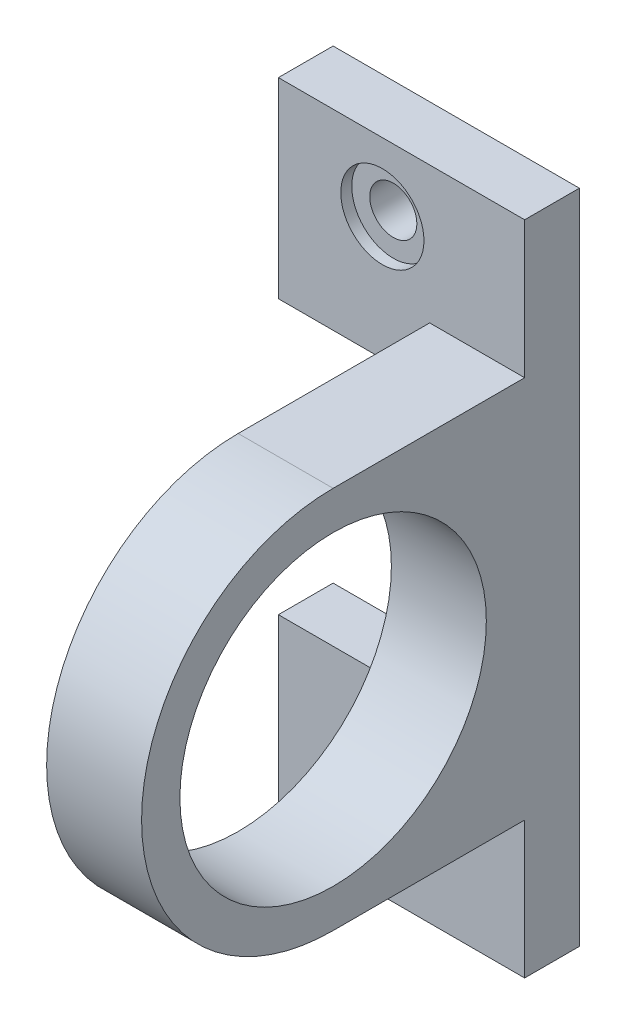
SolidWorks part; units mm, degrees
ref_plane "前视基准面" through (0, 0, 0) normal (0, 0, 1) x (1, 0, 0)
ref_plane "上视基准面" through (0, 0, 0) normal (0, 1, 0) x (1, 0, 0)
ref_plane "右视基准面" through (0, 0, 0) normal (1, 0, 0) x (0, 0, -1)
sketch "草图2" plane through (0, 0, 0) normal (0, 0, 1) x (1, 0, 0)
  line L0 (-14.7736, 24.3382) -> (-14.7736, -35.6618)
  line L1 (-14.7736, -35.6618) -> (30.2264, -35.6618)
  line L2 (7.7264, -35.6618) -> (7.7264, -18.1618)
  line L3 (21.55, -18.1618) -> (-6.0971, -18.1618)
  line L4 (-6.0971, -18.1618) -> (-6.0971, 6.8382)
  line L5 (-6.0971, 6.8382) -> (21.55, 6.8382)
  line L6 (7.7264, 6.8382) -> (7.7264, 24.3382)
  line L7 (30.2264, 24.3382) -> (-14.7736, 24.3382)
  line L8 (7.7264, 28.8603) -> (7.7264, -39.8897) construction
  line L9 (21.55, -18.1618) -> (21.55, 6.8382)
  line L10 (30.2264, 24.3382) -> (30.2264, -35.6618)
  line L11 (-18.1559, -5.6618) -> (33.2411, -5.6618) construction
  line L12 (44.0218, -5.6618) -> (44.0218, 26.2521) construction
  point P16 (-6.0971, -5.6618)
  point P17 (-14.7736, -5.6618)
  dimension "D1" = 45
  dimension "D2" = 25
  dimension "D3" = 60
extrude "凸台-拉伸2" add sketch "草图2" along normal blind 5 contours L6 L7 L0 L1 L2 L3 L4 L5 | L10 L7 L6 L5 L9 L3 L2 L1 region at (-3.5236, 23.6974, 0) region at (18.9764, 23.6974, 0)
sketch "草图4" plane through (0, 0, 5) normal (0, 0, 1) x (1, 0, 0)
  line L0 (-18.165, -5.6618) -> (33.9165, -5.6618) construction
  line L1 (-14.7736, 24.3382) -> (-14.7736, -35.6618) construction
  line L2 (-14.7736, -23.1618) -> (-6.0971, -23.1618)
  line L3 (-14.7736, -23.1618) -> (-14.7736, 11.8382)
  line L4 (-14.7736, 11.8382) -> (-6.0971, 11.8382)
  line L5 (-6.0971, -23.1618) -> (-6.0971, 11.8382)
  line L6 (-6.0971, -18.1618) -> (-6.0971, 6.8382) construction
  line L7 (7.7264, -39.813) -> (7.7264, 28.1228) construction
  line L8 (30.2264, 11.8382) -> (21.55, 11.8382)
  line L9 (21.55, -23.1618) -> (21.55, 11.8382)
  line L10 (30.2264, -23.1618) -> (21.55, -23.1618)
  line L11 (30.2264, -23.1618) -> (30.2264, 11.8382)
  point P17 (-14.7736, -5.6618)
  dimension "D1" = 35
extrude "凸台-拉伸15" add sketch "草图4" along normal blind 35
sketch "草图5" plane through (-14.7736, 0, 0) normal (-1, 0, 0) x (0, 0, 1)
  line L0 (0, -5.6618) -> (40, -5.6618)
  line L1 (0, 24.3382) -> (0, -35.6618) construction
  line L2 (40, 11.8382) -> (40, -23.1618) construction
  line L3 (22.5, 11.8382) -> (40, 11.8382)
  line L4 (40, 11.8382) -> (40, -23.1618)
  line L5 (40, -23.1618) -> (22.5, -23.1618)
  circle A0 centre (22.5, -5.6618) radius 17.5
  line M5 (5, -23.1618) -> (40, -23.1618)
  line M6 (40, -23.1618) -> (40, 11.8382)
  line M7 (40, 11.8382) -> (5, 11.8382)
  dimension "D1" = 35
extrude "切除-拉伸1" cut sketch "草图5" against normal blind 45 contours A0 M5 M6 | A0 M6 M7 region at (-14.7736, 7.9293, 36.0911) region at (-14.7736, -19.2528, 36.0911)
sketch "草图6" plane through (-14.7736, 0, 0) normal (-1, 0, 0) x (0, 0, 1)
  circle A0 centre (22.5, -5.6618) radius 14
  dimension "D1" = 28
extrude "切除-拉伸2" cut sketch "草图6" against normal blind 45
fillet "圆角1" radius 5 4 edges at (-6.0971, 6.8382, 2.5) (21.55, 6.8382, 2.5) (-6.0971, -18.1618, 2.5) (21.55, -18.1618, 2.5)
sketch "草图7" plane through (-6.0971, 0, 0) normal (1, 0, 0) x (0, 0, -1)
  circle A0 centre (-22.5, -5.6618) radius 15
  circle A1 centre (-22.5, -5.6618) radius 13
extrude "凸台-拉伸16" add sketch "草图7" against normal blind 1
sketch "草图8" plane through (21.55, 0, 0) normal (-1, 0, 0) x (0, 0, 1)
  circle A0 centre (22.5, -5.6618) radius 15
  circle A1 centre (22.5, -5.6618) radius 10
sketch "草图9" plane through (0, 0, 5) normal (0, 0, 1) x (1, 0, 0)
  line L0 (7.7264, 24.3382) -> (7.7264, -35.6618)
  line L13 (30.2264, 24.3382) -> (-14.7736, 24.3382) construction
  line L14 (-14.7736, -35.6618) -> (30.2264, -35.6618) construction
sketch "草图11" plane through (0, 0, 5) normal (0, 0, 1) x (1, 0, 0)
  line L0 (-14.7736, 18.0882) -> (30.2264, 18.0882)
  line L1 (-14.7736, 24.3382) -> (-14.7736, 11.8382) construction
  line L2 (30.2264, 24.3382) -> (30.2264, 11.8382) construction
  line L3 (7.7264, 24.3382) -> (7.7264, -35.6618) construction
  line L4 (30.2264, 24.3382) -> (-14.7736, 24.3382) construction
  line L5 (-14.7736, -35.6618) -> (30.2264, -35.6618) construction
  line L6 (7.7264, -5.6618) -> (45.6912, -5.6618) construction
  line L10 (-14.7736, -29.4118) -> (30.2264, -29.4118)
  line L11 (-14.7736, -23.1618) -> (-14.7736, -35.6618) construction
  point P4 (-1.7736, 18.0882)
  point P16 (-1.7736, -29.4118)
  point P18 (17.2264, -29.4118)
  point P25 (17.2264, 18.0882)
  dimension "D1" = 13
split "分割1" trim tools "草图9" bodies to split 111 resulting bodies 117 118
delete or keep bodies "实体-删除/保留 2" type delete bodies bodies 117
hole_wizard "打孔尺寸(%根据六角头螺)栓 全螺纹的类型1" positions "3D草图2" profile "草图13" counterbore size "M4" standard "GB"
sketch3d "3D草图2"
  point P0 (17.2264, 18.0882, 5)
  point P3 (17.2264, -29.4118, 5)
sketch "草图13" plane through (17.2264, 18.0882, 5) normal (1, 0, 0) x (0, -1, 0)
  line L0 (0, 0) -> (0, 6.2919)
  line L1 (0, 6.2919) -> (2.15, 5)
  line L2 (2.15, 5) -> (2.15, 1)
  line L3 (2.15, 1) -> (3.8, 1)
  line L4 (3.8, 1) -> (3.8, 0)
  line L5 (3.8, 0) -> (0, 0)
  line L10 (0, 6.2919) -> (-2.15, 5) construction
  line L11 (0, -6.35) -> (0, 107.95) construction
  dimension "孔直径" = 4.3
  dimension "孔深度" = 5
  dimension "柱形沉头孔直径" = 7.6
  dimension "柱形沉头孔深度" = 1
  dimension "导头角度" = 118
